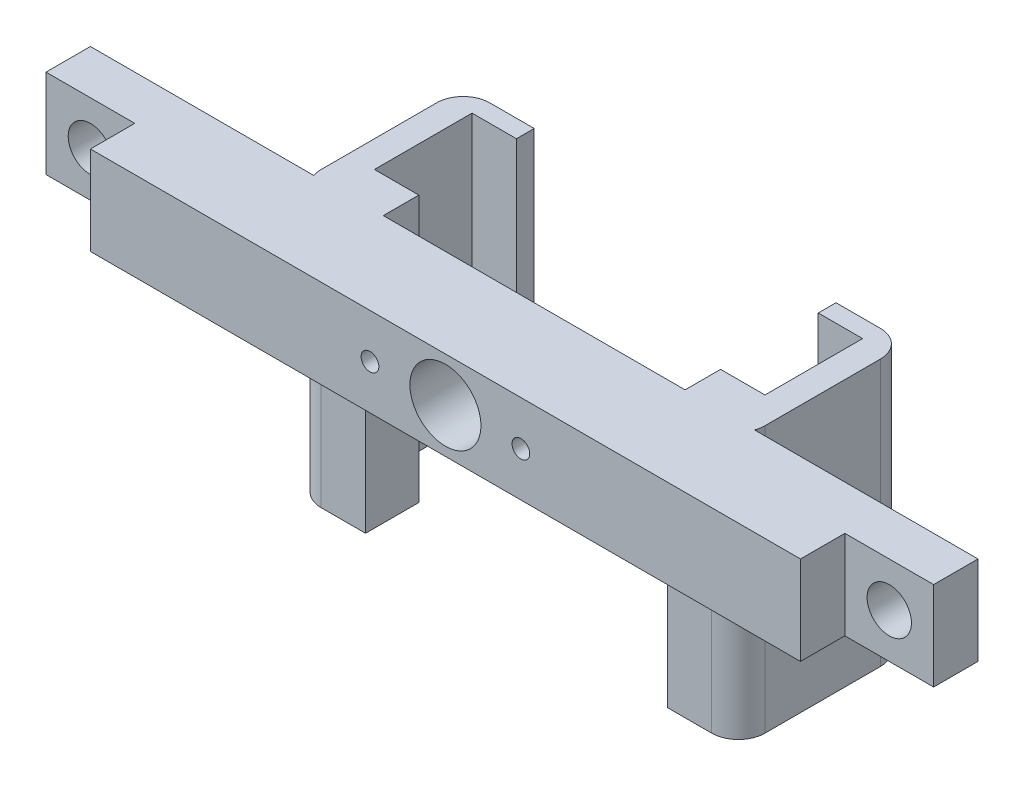
SolidWorks part; units mm, degrees
ref_plane "Front Plane" through (0, 0, 0) normal (0, 0, 1) x (1, 0, 0)
ref_plane "Top Plane" through (0, 0, 0) normal (0, 1, 0) x (1, 0, 0)
ref_plane "Right Plane" through (0, 0, 0) normal (1, 0, 0) x (0, 0, -1)
sketch "Sketch1" plane through (0, 0, 0) normal (0, 0, 1) x (1, 0, 0)
  line L1 (-50, 5) -> (50, 5)
  line L2 (-50, 5) -> (-50, -5)
  line L3 (-50, -5) -> (50, -5)
  line L4 (50, 5) -> (50, -5)
  line L5 (-50, 5) -> (50, -5) construction
  line L6 (-50, -5) -> (50, 5) construction
  point P0 (0, 0)
  dimension "D1" = 100
  dimension "D2" = 10
extrude "Boss-Extrude1" add sketch "Sketch1" along normal blind 10
sketch "Sketch2" plane through (0, 5, 0) normal (0, 1, 0) x (1, 0, 0)
  line L5 (-50, -10) -> (-40, -10)
  line L6 (-50, -10) -> (-50, -5)
  line L7 (-50, -5) -> (-40, -5)
  line L8 (-40, -10) -> (-40, -5)
  dimension "D1" = 10
  dimension "D2" = 5
sketch "Sketch6" plane through (0, 0, 0) normal (0, 0, -1) x (-1, 0, 0)
  line L0 (0, 5) -> (0, -5) construction
  line L1 (-25, 5) -> (-25, -5)
  line L3 (-25, 5) -> (-22, 5)
  line L4 (-50, 5) -> (-50, -5)
  line L5 (-50, -5) -> (50, -5)
  line L6 (-50, 5) -> (-50, -5)
  line L7 (50, 5) -> (-50, 5)
  line L9 (-50, -5) -> (50, -5)
  line L11 (50, 5) -> (-50, 5)
  line L12 (-22, 5) -> (-22, -5)
  line L13 (-22, -5) -> (-25, -5)
  line L17 (50, -5) -> (50, 5)
  line L18 (50, -5) -> (50, 5)
  line M11 (-50, -5) -> (50, -5)
  line M13 (50, 5) -> (-50, 5)
  dimension "D2" = 25
  dimension "D3" = 3
  dimension "D1" = 0
extrude "Boss-Extrude2" add sketch "Sketch6" along normal blind 17 contours L12 L1 M13 M11 region at (23.5, 0, 0)
sketch "Sketch8" plane through (22, 0, 0) normal (-1, 0, 0) x (0, 0, 1)
  line L0 (-17, -5) -> (0, -5) construction
  line L1 (-17, 5) -> (-15, 5)
  line L2 (-17, 5) -> (-17, -5)
  line L3 (-17, -5) -> (-15, -5)
  line L4 (-15, 5) -> (-15, -5)
  dimension "D1" = 2
extrude "Boss-Extrude3" add sketch "Sketch8" along normal blind 5
sketch "Sketch9" plane through (0, -5, 0) normal (0, -1, 0) x (1, 0, 0)
  line L0 (17, -17) -> (17, 0) construction
  line L1 (-50, 0) -> (22, 0) construction
  line L2 (17, 0) -> (22, 0)
  line L4 (17, 0) -> (17, 2)
  line L5 (17, 2) -> (25, 2)
  line L6 (25, 0) -> (25, 2)
  line L7 (22, 0) -> (22, -15)
  line L8 (22, -15) -> (17, -15)
  line L9 (17, -15) -> (17, -17)
  line L10 (17, -17) -> (25, -17)
  line L11 (25, -17) -> (25, 0)
  line L12 (25, 0) -> (25, 2)
  line L13 (-50, 10) -> (-50, 0) construction
  line L14 (-50, 10) -> (50, 10) construction
  line M16 (-50, 0) -> (22, 0)
  line M17 (22, 0) -> (22, -15)
  line M18 (22, -15) -> (17, -15)
  line M19 (17, -15) -> (17, -17)
  line M20 (17, -17) -> (25, -17)
  line M21 (25, -17) -> (25, 0)
  dimension "D1" = 8
  dimension "D2" = 2
  dimension "D3" = 2
extrude "Boss-Extrude4" add sketch "Sketch9" along normal blind 20 contours L6 L5 L4 M21 M16 M17 M18 M19 M20 region at (22.461, -5, -7.5)
mirror "Mirror3" about plane through (0, 0, 0) normal (1, 0, 0) of "Boss-Extrude4", "Boss-Extrude3", "Boss-Extrude2"
extrude "Cut-Extrude1" cut sketch "Sketch2" against normal blind 10
mirror "Mirror4" about plane through (0, 0, 0) normal (1, 0, 0) of "Cut-Extrude1"
sketch "Sketch10" plane through (0, 0, 5) normal (0, 0, 1) x (1, 0, 0)
  line L0 (50, -5) -> (50, 5) construction
  line L1 (40, -5) -> (50, -5) construction
  circle A0 centre (45, 0) radius 2.5
  dimension "D1" = 5
  dimension "D2" = 5
  dimension "D3" = 5
extrude "Cut-Extrude2" cut sketch "Sketch10" against normal up to next
mirror "Mirror5" about plane through (0, 0, 0) normal (1, 0, 0) of "Cut-Extrude2"
sketch "Sketch12" plane through (0, 0, 0) normal (0, 0, -1) x (-1, 0, 0)
  line L0 (0, 5) -> (0, -5) construction
  line L1 (-22, 5) -> (22, 5) construction
  line L2 (17, -5) -> (-17, -5) construction
sketch "Sketch13" plane through (0, 0, 0) normal (0, 0, -1) x (-1, 0, 0)
  line L0 (0, 0) -> (-8.5, 0) construction
  line L1 (0, 0) -> (8.5, 0) construction
  circle A0 centre (0, 0) radius 4
  circle A1 centre (-8.5, 0) radius 1
  circle A2 centre (8.5, 0) radius 1
  dimension "D1" = 8
  dimension "D4" = 2
  dimension "D5" = 2
  dimension "D2" = 8.5
  dimension "D3" = 8.5
extrude "Cut-Extrude3" cut sketch "Sketch13" against normal through all
fillet "Fillet1" radius 3 2 edges at (25, -10, -17) (-25, -10, -17)
fillet "Fillet2" radius 3 2 edges at (-25, -15, 2) (25, -15, 2)
sketch "Sketch14" plane through (0, 0, 0) normal (0, 0, -1) x (-1, 0, 0)
  line L6 (22, 5) -> (17, 5)
  line L7 (22, 5) -> (22, -25)
  line L8 (22, -25) -> (17, -25)
  line L9 (17, 5) -> (17, -25)
extrude "Boss-Extrude5" add sketch "Sketch14" along normal blind 4
mirror "Mirror6" about plane through (0, 0, 0) normal (1, 0, 0) of "Boss-Extrude5"
